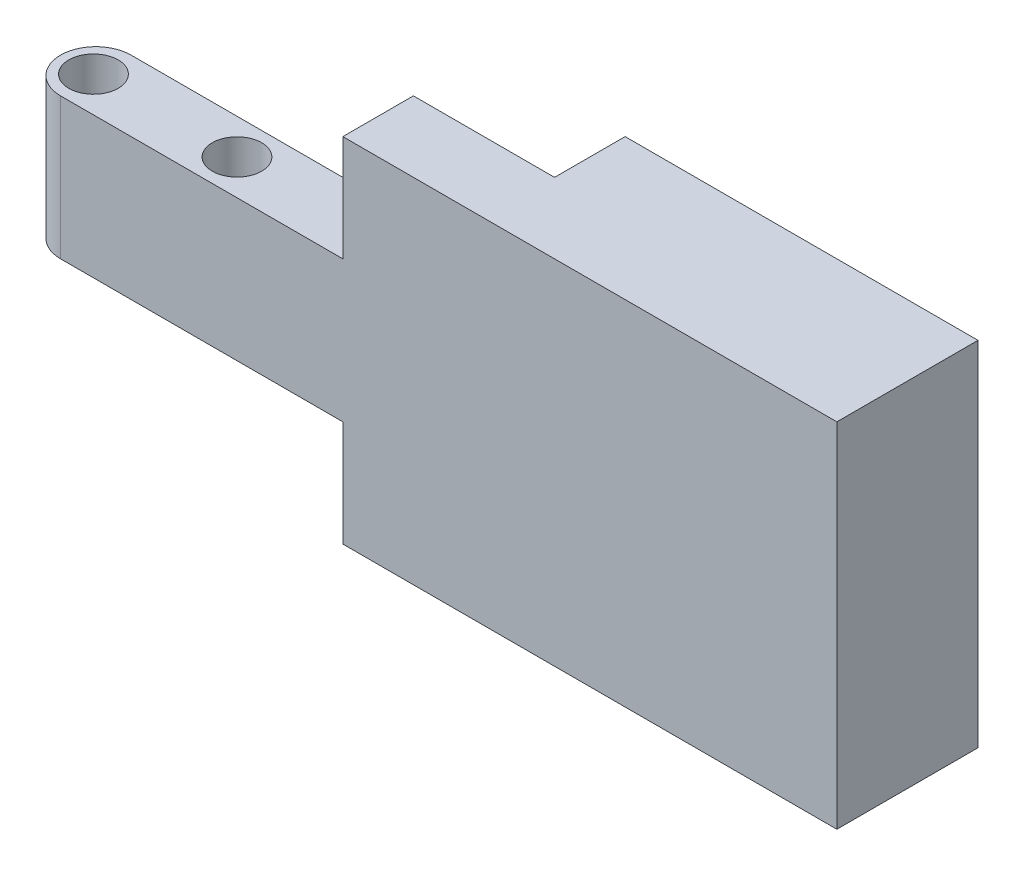
SolidWorks part; units mm, degrees
ref_plane "Front Plane" through (0, 0, 0) normal (0, 0, 1) x (1, 0, 0)
ref_plane "Top Plane" through (0, 0, 0) normal (0, 1, 0) x (1, 0, 0)
ref_plane "Right Plane" through (0, 0, 0) normal (1, 0, 0) x (0, 0, -1)
sketch "Sketch1" plane through (0, 0, 0) normal (0, 1, 0) x (1, 0, 0)
  line L1 (-35, -5) -> (35, -5)
  line L2 (-35, -5) -> (-35, 5)
  line L3 (-35, 5) -> (35, 5)
  line L4 (35, -5) -> (35, 5)
  line L5 (-35, -5) -> (35, 5) construction
  line L6 (-35, 5) -> (35, -5) construction
  point P0 (0, 0)
  dimension "D1" = 10
  dimension "D2" = 70
extrude "Boss-Extrude1" add sketch "Sketch1" along normal blind 25 and the other way blind 25 contours L2 L1 L4 L3
sketch "Sketch2" plane through (0, 0, 0) normal (0, 1, 0) x (1, 0, 0)
  line L0 (-75, 5) -> (-35, 5)
  line L1 (-35, 5) -> (-35, -5)
  line L2 (-35, -5) -> (-75, -5)
  arc A0 (-75, 5) -> (-75, -5) centre (-75, 0) ccw
  dimension "D1" = 10
  dimension "D2" = 75
extrude "Boss-Extrude2" add sketch "Sketch2" along normal blind 10 and the other way blind 10
sketch "Sketch3" plane through (0, 0, 0) normal (0, 1, 0) x (1, 0, 0)
  circle A0 centre (-75.3332, 0) radius 3.5
  circle A1 centre (-55, 0) radius 3.5
  dimension "D1" = 7
  dimension "D2" = 7
  dimension "D3" = 75.3332
  dimension "D4" = 55
extrude "Cut-Extrude1" cut sketch "Sketch3" against normal blind 16 and the other way blind 19
sketch "Sketch4" plane through (0, 0, 0) normal (0, 0, 1) x (1, 0, 0)
  line L0 (20.4059, 0) -> (-20.4059, 0) construction
  line L1 (35, -25) -> (-15, -25)
  line L2 (35, -25) -> (35, 25)
  line L3 (35, 25) -> (-15, 25)
  line L4 (-15, -25) -> (-15, 25)
  line L5 (35, -25) -> (-15, 25) construction
  line L6 (35, 25) -> (-15, -25) construction
  line L7 (-35, 25) -> (35, 25) construction
  point P0 (10, 0)
  dimension "D1" = 10
  dimension "D2" = 50
extrude "Boss-Extrude3" add sketch "Sketch4" against normal blind 15
